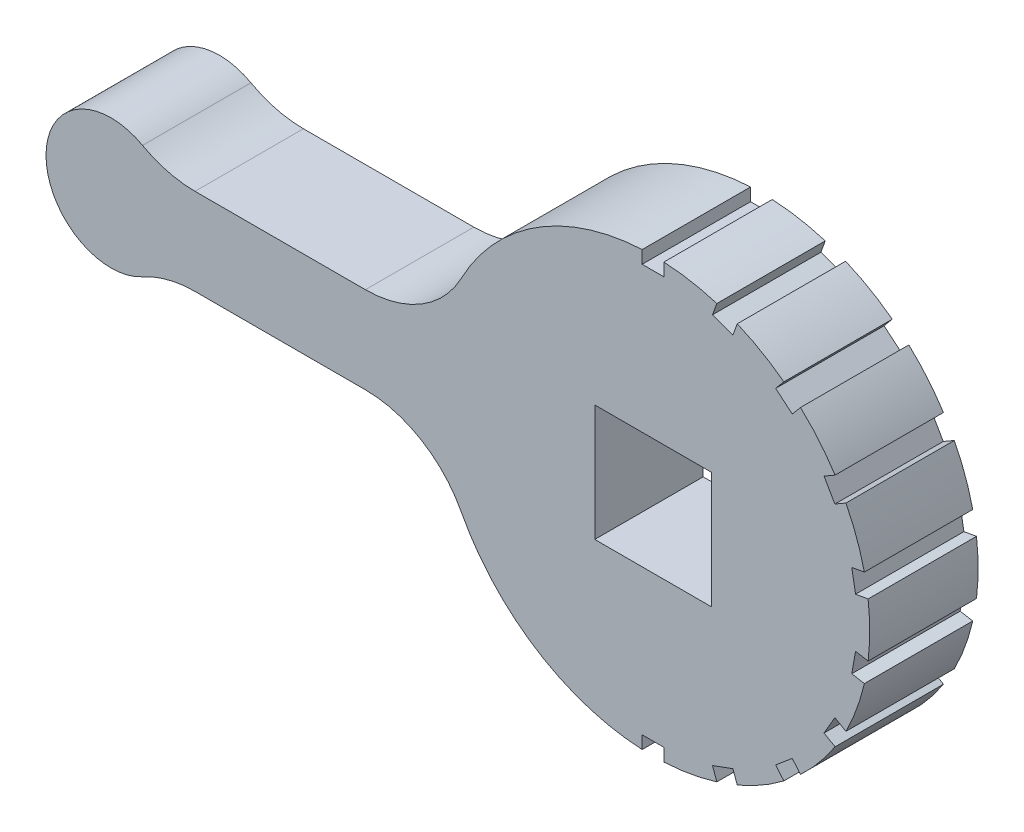
SolidWorks part; units mm, degrees
ref_plane "Front Plane" through (0, 0, 0) normal (0, 0, 1) x (1, 0, 0)
ref_plane "Top Plane" through (0, 0, 0) normal (0, 1, 0) x (1, 0, 0)
ref_plane "Right Plane" through (0, 0, 0) normal (1, 0, 0) x (0, 0, -1)
sketch "Sketch4" plane through (0, 0, 0) normal (0, 0, 1) x (1, 0, 0)
  line L0 (0, 0) -> (0, 10) construction
  line L1 (0, 0) -> (-25, 0) construction
  dimension "D1" = 10
  dimension "D2" = 25
sketch "L" plane through (0, 0, 0) normal (0, 0, 1) x (1, 0, 0)
  line L0 (0, 0) -> (0, -10) construction
  line L1 (0, 0) -> (25, 0) construction
  line L2 (0, 0) -> (0, 10) construction
  line L3 (0, 0) -> (-28.8314, 0) construction
  spline S1 degree 4 poles (2.2591, 8.364) (2.1926, 8.4214) (2.0587, 8.5352) (1.8546, 8.7034) (1.5802, 8.9204) (1.2974, 9.1337) (1.0216, 9.3339) (0.7194, 9.5414) (0.4674, 9.7102) (0.1096, 9.9341) (-0.0654, 10.0403) (-0.3706, 10.2188) (-0.6083, 10.3515) (-0.824, 10.4676) (-1.0114, 10.5652) (-1.1995, 10.6607) (-1.3883, 10.7539) (-1.6102, 10.8597) (-1.9296, 11.0058) (-2.3165, 11.1729) (-2.773, 11.3558) (-3.565, 11.6445) (-4.7747, 12.015) (-6.4247, 12.3753) (-8.5252, 12.5961) (-10.7776, 12.569) (-12.8586, 12.306) (-14.9014, 11.8356) (-16.8881, 11.1667) (-18.8017, 10.3091) (-20.7499, 9.1804) (-22.5734, 7.8599) (-24.0462, 6.5519) (-25.2125, 5.3327) (-26.0266, 4.3648) (-26.5431, 3.6986) (-26.9559, 3.1302) (-27.2753, 2.6678) (-27.5837, 2.1982) (-27.844, 1.7808) (-28.06, 1.4193) (-28.2356, 1.1148) (-28.3737, 0.8687) (-28.5054, 0.628) (-28.6406, 0.3732) (-28.8052, 0.0536) (-28.9094, -0.1553) (-29.1337, -0.6169) (-29.2818, -0.9447) (-29.4691, -1.367) (-29.6265, -1.746) (-29.7889, -2.1515) (-29.9383, -2.5471) (-30.0479, -2.8511) (-30.1178, -3.0528) (-30.1521, -3.1538) knots 0 0 0 0 0 0.008697 0.017393 0.02609 0.034786 0.043356 0.051926 0.060495 0.069065 0.076013 0.082961 0.089909 0.096858 0.100332 0.103806 0.110754 0.117702 0.12465 0.138547 0.152443 0.16634 0.208029 0.263615 0.3192 0.374786 0.430372 0.470684 0.52627 0.581855 0.637441 0.693027 0.748612 0.776405 0.804198 0.818095 0.831991 0.845887 0.859784 0.87368 0.880628 0.887577 0.894525 0.901473 0.908421 0.91537 0.925948 0.936527 0.947106 0.957685 0.968264 0.978842 0.989421 1 1 1 1 1 construction
  spline S2 degree 4 poles (0, 10) (-0.0509, 10.0307) (-0.1543, 10.0923) (-0.3706, 10.2188) (-0.6083, 10.3515) (-0.824, 10.4676) (-1.0114, 10.5652) (-1.1995, 10.6607) (-1.3883, 10.7539) (-1.6102, 10.8597) (-1.9296, 11.0058) (-2.3165, 11.1729) (-2.773, 11.3558) (-3.565, 11.6445) (-4.7747, 12.015) (-6.4247, 12.3753) (-8.5252, 12.5961) (-10.7776, 12.569) (-12.8586, 12.306) (-14.9014, 11.8356) (-16.8881, 11.1667) (-18.8017, 10.3091) (-20.7499, 9.1804) (-22.5734, 7.8599) (-24.0462, 6.5519) (-25.2125, 5.3327) (-26.0266, 4.3648) (-26.5431, 3.6986) (-26.9559, 3.1302) (-27.2753, 2.6678) (-27.5837, 2.1982) (-27.844, 1.7808) (-28.06, 1.4193) (-28.2356, 1.1148) (-28.3737, 0.8687) (-28.5054, 0.628) (-28.6406, 0.3732) (-28.7498, 0.1612) (-28.8047, 0.0531) (-28.8314, 0) knots 0.069065 0.069065 0.069065 0.069065 0.069065 0.076013 0.082961 0.089909 0.096858 0.100332 0.103806 0.110754 0.117702 0.12465 0.138547 0.152443 0.16634 0.208029 0.263615 0.3192 0.374786 0.430372 0.470684 0.52627 0.581855 0.637441 0.693027 0.748612 0.776405 0.804198 0.818095 0.831991 0.845887 0.859784 0.87368 0.880628 0.887577 0.894525 0.901473 0.908421 0.91537 0.91537 0.91537 0.91537 0.91537
  dimension "D1" = 10
  dimension "D2" = 25
sketch "Sketch2" plane through (0, 0, 0) normal (0, 0, 1) x (1, 0, 0)
  line L0 (0, 10) -> (10, 0)
  line L1 (10, 0) -> (-28.8314, 0)
  spline S0 degree 4 poles (1711.3489, -1024.1766) (-44.469, 36.4589) (3.6301, 7.7183) (0.663, 9.6418) (-0.6083, 10.3515) (-0.824, 10.4676) (-1.0114, 10.5652) (-1.1995, 10.6607) (-1.3883, 10.7539) (-1.6102, 10.8597) (-1.9296, 11.0058) (-2.3165, 11.1729) (-2.773, 11.3558) (-3.565, 11.6445) (-4.7747, 12.015) (-6.4247, 12.3753) (-8.5252, 12.5961) (-10.7776, 12.569) (-12.8586, 12.306) (-14.9014, 11.8356) (-16.8881, 11.1667) (-18.8017, 10.3091) (-20.7499, 9.1804) (-22.5734, 7.8599) (-24.0462, 6.5519) (-25.2125, 5.3327) (-26.0266, 4.3648) (-26.5431, 3.6986) (-26.9559, 3.1302) (-27.2753, 2.6678) (-27.5837, 2.1982) (-27.844, 1.7808) (-28.06, 1.4193) (-28.2356, 1.1148) (-28.3737, 0.8687) (-28.5054, 0.628) (-29.2767, -0.8255) (-30.4266, -3.3205) (-7.8225, 41.2196) (-925.9153, -1786.783) knots -0.05179 -0.05179 -0.05179 -0.05179 -0.05179 0.076013 0.082961 0.089909 0.096858 0.100332 0.103806 0.110754 0.117702 0.12465 0.138547 0.152443 0.16634 0.208029 0.263615 0.3192 0.374786 0.430372 0.470684 0.52627 0.581855 0.637441 0.693027 0.748612 0.776405 0.804198 0.818095 0.831991 0.845887 0.859784 0.87368 0.880628 0.887577 0.894525 0.901473 0.908421 1.046125 1.046125 1.046125 1.046125 1.046125 only from (0, 10) to (-28.8314, 0) construction
  spline S1 degree 4 poles (0, 10) (-0.0509, 10.0307) (-0.1543, 10.0923) (-0.3706, 10.2188) (-0.6083, 10.3515) (-0.824, 10.4676) (-1.0114, 10.5652) (-1.1995, 10.6607) (-1.3883, 10.7539) (-1.6102, 10.8597) (-1.9296, 11.0058) (-2.3165, 11.1729) (-2.773, 11.3558) (-3.565, 11.6445) (-4.7747, 12.015) (-6.4247, 12.3753) (-8.5252, 12.5961) (-10.7776, 12.569) (-12.8586, 12.306) (-14.9014, 11.8356) (-16.8881, 11.1667) (-18.8017, 10.3091) (-20.7499, 9.1804) (-22.5734, 7.8599) (-24.0462, 6.5519) (-25.2125, 5.3327) (-26.0266, 4.3648) (-26.5431, 3.6986) (-26.9559, 3.1302) (-27.2753, 2.6678) (-27.5837, 2.1982) (-27.844, 1.7808) (-28.06, 1.4193) (-28.2356, 1.1148) (-28.3737, 0.8687) (-28.5054, 0.628) (-28.6406, 0.3732) (-28.7498, 0.1612) (-28.8047, 0.0531) (-28.8314, 0) knots 0.069065 0.069065 0.069065 0.069065 0.069065 0.076013 0.082961 0.089909 0.096858 0.100332 0.103806 0.110754 0.117702 0.12465 0.138547 0.152443 0.16634 0.208029 0.263615 0.3192 0.374786 0.430372 0.470684 0.52627 0.581855 0.637441 0.693027 0.748612 0.776405 0.804198 0.818095 0.831991 0.845887 0.859784 0.87368 0.880628 0.887577 0.894525 0.901473 0.908421 0.91537 0.91537 0.91537 0.91537 0.91537
  dimension "D1" = 10
extrude "Boss-Extrude1" [suppressed] add sketch "Sketch2" against normal blind 10
mirror "Mirror1" [suppressed] of bodies 101
fillet "Fillet1" [suppressed] radius 5
sketch "Sketch5" plane through (0, 0, 0) normal (0, 0, 1) x (1, 0, 0)
  line L0 (0, 10) -> (0, 0) construction
  line L1 (0, 0) -> (-25, 0)
  line L2 (0, 0) -> (10, 0)
  arc A0 (10, 0) -> (0, 10) centre (0, 0) ccw
  ellipse E0 centre (0, 0) end of major axis (-25, 0) minor radius 10 (0, 10) -> (-25, 0) ccw
extrude "Boss-Extrude5" [suppressed] add sketch "Sketch5" against normal blind 10 contours E0 L1 L2 A0
mirror "Mirror2" [suppressed] of bodies 107 108
sketch "Sketch3" plane through (0, 0, 0) normal (0, 0, 1) x (1, 0, 0)
  line L1 (2.687, -2.687) -> (-2.687, -2.687)
  line L2 (2.687, -2.687) -> (2.687, 2.687)
  line L3 (2.687, 2.687) -> (-2.687, 2.687)
  line L4 (-2.687, -2.687) -> (-2.687, 2.687)
  line L5 (2.687, -2.687) -> (-2.687, 2.687) construction
  line L6 (2.687, 2.687) -> (-2.687, -2.687) construction
  circle A0 centre (0, 0) radius 3.8 construction
  dimension "D1" = 7.6
extrude "Cut-Extrude2" [suppressed] cut sketch "Sketch3" against normal through all contours L3 L4 L1 L2
sketch "Sketch6" plane through (0, 0, 0) normal (0, 0, 1) x (1, 0, 0)
  line L0 (-22.7639, 2) -> (-9.798, 2)
  line L1 (-9.798, -2) -> (-22.7639, -2)
  arc A0 (-9.798, -2) -> (-9.798, 2) centre (0, 0) ccw
  arc A1 (-22.7639, 2) -> (-22.7639, -2) centre (-25, 0) ccw
  dimension "D1" = 6
  dimension "D2" = 4
extrude "Boss-Extrude8" add sketch "Sketch6" along normal blind 5
extrude "Cut-Extrude3" cut sketch "Sketch3<3>" along normal through all contours L3 L4 L1 L2
sketch "Sketch3<3>" plane through (0, 0, 0) normal (0, 0, 1) x (1, 0, 0) same geometry as "Sketch3"
fillet "Fillet4" radius 5 4 edges at (-22.7639, 2, 2.5) (-9.798, -2, 2.5) (-22.7639, -2, 2.5) (-9.798, 2, 2.5)
sketch "Sketch7" plane through (0, 0, 5) normal (0, 0, 1) x (1, 0, 0)
  line L0 (0, 0) -> (0, 10) construction
  line L1 (3.2135, 10.2908) -> (4.1531, 9.9488)
  line L2 (-0.5, 10.7692) -> (0.5, 10.7692)
  line L3 (-0.5, 10.7692) -> (-0.5, 9.3979)
  line L4 (-0.5, 9.3979) -> (0.5, 9.3979)
  line L5 (0.5, 10.7692) -> (0.5, 9.3979)
  line L6 (3.2135, 10.2908) -> (2.7444, 9.0021)
  line L7 (4.1531, 9.9488) -> (3.6841, 8.6601)
  line L8 (2.7444, 9.0021) -> (3.6841, 8.6601)
  line L9 (6.5393, 8.5711) -> (7.3054, 7.9283)
  line L10 (6.5393, 8.5711) -> (5.6578, 7.5206)
  line L11 (7.3054, 7.9283) -> (6.4239, 6.8778)
  line L12 (5.6578, 7.5206) -> (6.4239, 6.8778)
  line L13 (9.0764, 5.8176) -> (9.5764, 4.9516)
  line L14 (9.0764, 5.8176) -> (7.8888, 5.132)
  line L15 (9.5764, 4.9516) -> (8.3888, 4.2659)
  line L16 (7.8888, 5.132) -> (8.3888, 4.2659)
  line L17 (10.5188, 2.3625) -> (10.6925, 1.3777)
  line L18 (10.5188, 2.3625) -> (9.1683, 2.1243)
  line L19 (10.6925, 1.3777) -> (9.3419, 1.1395)
  line L20 (9.1683, 2.1243) -> (9.3419, 1.1395)
  line L21 (10.6925, -1.3777) -> (10.5188, -2.3625)
  line L22 (10.6925, -1.3777) -> (9.3419, -1.1395)
  line L23 (10.5188, -2.3625) -> (9.1683, -2.1243)
  line L24 (9.3419, -1.1395) -> (9.1683, -2.1243)
  line L25 (9.5764, -4.9516) -> (9.0764, -5.8176)
  line L26 (9.5764, -4.9516) -> (8.3888, -4.2659)
  line L27 (9.0764, -5.8176) -> (7.8888, -5.132)
  line L28 (8.3888, -4.2659) -> (7.8888, -5.132)
  line L29 (7.3054, -7.9283) -> (6.5393, -8.5711)
  line L30 (7.3054, -7.9283) -> (6.4239, -6.8778)
  line L31 (6.5393, -8.5711) -> (5.6578, -7.5206)
  line L32 (6.4239, -6.8778) -> (5.6578, -7.5206)
  line L33 (4.1531, -9.9488) -> (3.2135, -10.2908)
  line L34 (4.1531, -9.9488) -> (3.6841, -8.6601)
  line L35 (3.2135, -10.2908) -> (2.7444, -9.0021)
  line L36 (3.6841, -8.6601) -> (2.7444, -9.0021)
  line L37 (0.5, -10.7692) -> (-0.5, -10.7692)
  line L38 (0.5, -10.7692) -> (0.5, -9.3979)
  line L39 (-0.5, -10.7692) -> (-0.5, -9.3979)
  line L40 (0.5, -9.3979) -> (-0.5, -9.3979)
  line L73 (-3.2135, -10.2908) -> (-4.1531, -9.9488) [skipped]
  line L74 (-3.2135, -10.2908) -> (-2.7444, -9.0021) [skipped]
  line L75 (-4.1531, -9.9488) -> (-3.6841, -8.6601) [skipped]
  line L76 (-2.7444, -9.0021) -> (-3.6841, -8.6601) [skipped]
  line L77 (-6.5393, -8.5711) -> (-7.3054, -7.9283) [skipped]
  line L78 (-6.5393, -8.5711) -> (-5.6578, -7.5206) [skipped]
  line L79 (-7.3054, -7.9283) -> (-6.4239, -6.8778) [skipped]
  line L80 (-5.6578, -7.5206) -> (-6.4239, -6.8778) [skipped]
  line L81 (-9.0764, -5.8176) -> (-9.5764, -4.9516) [skipped]
  line L82 (-9.0764, -5.8176) -> (-7.8888, -5.132) [skipped]
  line L83 (-9.5764, -4.9516) -> (-8.3888, -4.2659) [skipped]
  line L84 (-7.8888, -5.132) -> (-8.3888, -4.2659) [skipped]
  line L85 (-10.5188, -2.3625) -> (-10.6925, -1.3777) [skipped]
  line L86 (-10.5188, -2.3625) -> (-9.1683, -2.1243) [skipped]
  line L87 (-10.6925, -1.3777) -> (-9.3419, -1.1395) [skipped]
  line L88 (-9.1683, -2.1243) -> (-9.3419, -1.1395) [skipped]
  line L89 (-10.6925, 1.3777) -> (-10.5188, 2.3625) [skipped]
  line L90 (-10.6925, 1.3777) -> (-9.3419, 1.1395) [skipped]
  line L91 (-10.5188, 2.3625) -> (-9.1683, 2.1243) [skipped]
  line L92 (-9.3419, 1.1395) -> (-9.1683, 2.1243) [skipped]
  line L93 (-9.5764, 4.9516) -> (-9.0764, 5.8176) [skipped]
  line L94 (-9.5764, 4.9516) -> (-8.3888, 4.2659) [skipped]
  line L95 (-9.0764, 5.8176) -> (-7.8888, 5.132) [skipped]
  line L96 (-8.3888, 4.2659) -> (-7.8888, 5.132) [skipped]
  line L97 (-7.3054, 7.9283) -> (-6.5393, 8.5711) [skipped]
  line L98 (-7.3054, 7.9283) -> (-6.4239, 6.8778) [skipped]
  line L99 (-6.5393, 8.5711) -> (-5.6578, 7.5206) [skipped]
  line L100 (-6.4239, 6.8778) -> (-5.6578, 7.5206) [skipped]
  line L101 (-4.1531, 9.9488) -> (-3.2135, 10.2908) [skipped]
  line L102 (-4.1531, 9.9488) -> (-3.6841, 8.6601) [skipped]
  line L103 (-3.2135, 10.2908) -> (-2.7444, 9.0021) [skipped]
  line L104 (-3.6841, 8.6601) -> (-2.7444, 9.0021) [skipped]
  point P77 (0, 0)
  dimension "D2" = 0.5
  dimension "D3" = 18
extrude "Cut-Extrude4" cut sketch "Sketch7" against normal up to vertex (5 mm away) up to point (-8.8443, -4.6667, 0)
equation "\"r1\"= 10"
equation "\"r2\"= 25"
equation "\"D1@Sketch4\"=\"r1\""
equation "\"D2@Sketch4\"=\"r2\""
equation "\"shaft\"= 7.6"
equation "\"D1@Sketch3\"=\"shaft\""
equation "\"t\"= 10"
equation "\"D1@Boss-Extrude1\"=\"t\""
equation "\"D1@Boss-Extrude5\"=\"t\""
equation "\"D1@L\" = \"r1\""
equation "\"D2@L\" = \"r2\""
